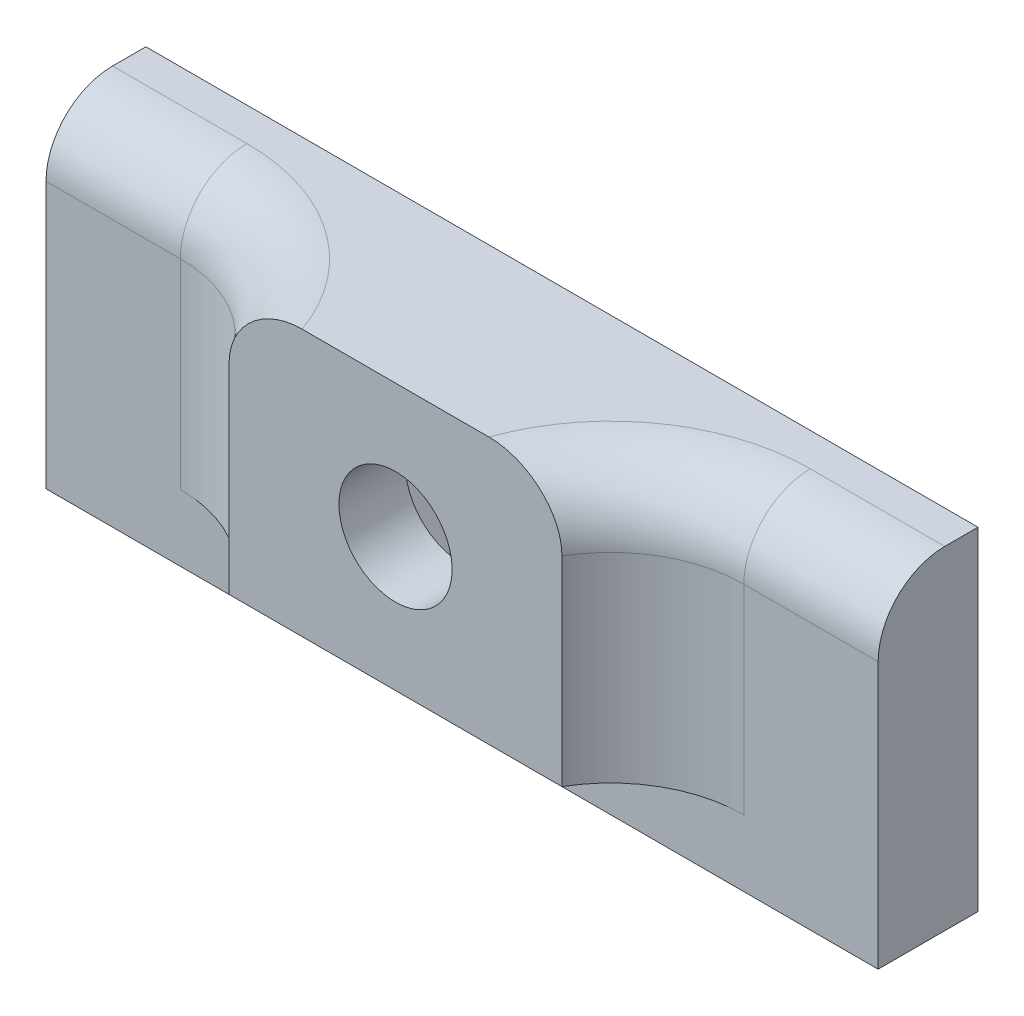
SolidWorks part; units mm, degrees
ref_plane "Front Plane" through (0, 0, 0) normal (0, 0, 1) x (1, 0, 0)
ref_plane "Top Plane" through (0, 0, 0) normal (0, 1, 0) x (1, 0, 0)
ref_plane "Right Plane" through (0, 0, 0) normal (1, 0, 0) x (0, 0, -1)
sketch "Sketch2" plane through (0, 0, 0) normal (0, 0, 1) x (1, 0, 0)
  line L1 (12.5, 0) -> (-12.5, 0)
  line L2 (12.5, 0) -> (12.5, 10)
  line L3 (12.5, 10) -> (-12.5, 10)
  line L4 (-12.5, 0) -> (-12.5, 10)
  dimension "D1" = 25
  dimension "D2" = 10
extrude "Boss-Extrude1" add sketch "Sketch2" along normal blind 3
sketch "Sketch5" plane through (0, 0, 3) normal (0, 0, 1) x (1, 0, 0)
  line L1 (-5, 10) -> (5, 10)
  line L2 (-5, 10) -> (-5, 2)
  line L3 (-5, 2) -> (5, 2)
  line L4 (5, 10) -> (5, 2)
  line L5 (-12.5, 0) -> (12.5, 0) construction
  line L6 (12.5, 10) -> (-12.5, 10) construction
  line L7 (0, 2) -> (0, 0) construction
  dimension "D1" = 2
  dimension "D2" = 10
sketch "Sketch8" plane through (0, 0, 0) normal (0, 0, -1) x (-1, 0, 0)
  line L1 (-12.5, 10) -> (12.5, 10) construction
  circle A0 centre (0, 6) radius 1.7
  dimension "D1" = 3.4
  dimension "D2" = 4
sketch "Sketch9" plane through (0, 0, 0) normal (0, 0, -1) x (-1, 0, 0)
  line L1 (3.4641, 6) -> (1.7321, 9)
  line L2 (1.7321, 9) -> (-1.7321, 9)
  line L3 (-1.7321, 9) -> (-3.4641, 6)
  line L4 (-3.4641, 6) -> (-1.7321, 3)
  line L5 (-1.7321, 3) -> (1.7321, 3)
  line L6 (1.7321, 3) -> (3.4641, 6)
  circle A0 centre (0, 6) radius 3 construction
  dimension "D1" = 6
extrude "Boss-Extrude3" add sketch "Sketch5" along normal blind 2
fillet "Fillet2" radius 4 2 edges at (5, 6, 3) (-5, 6, 3)
extrude "Cut-Extrude3" cut sketch "Sketch8" against normal through all
extrude "Cut-Extrude4" cut sketch "Sketch9" against normal blind 3
fillet "Fillet3" radius 2 4 edges at (6.4641, 10, 3.5359) (-10.4821, 10, 3) (10.4821, 10, 3) (-6.4641, 10, 3.5359)
